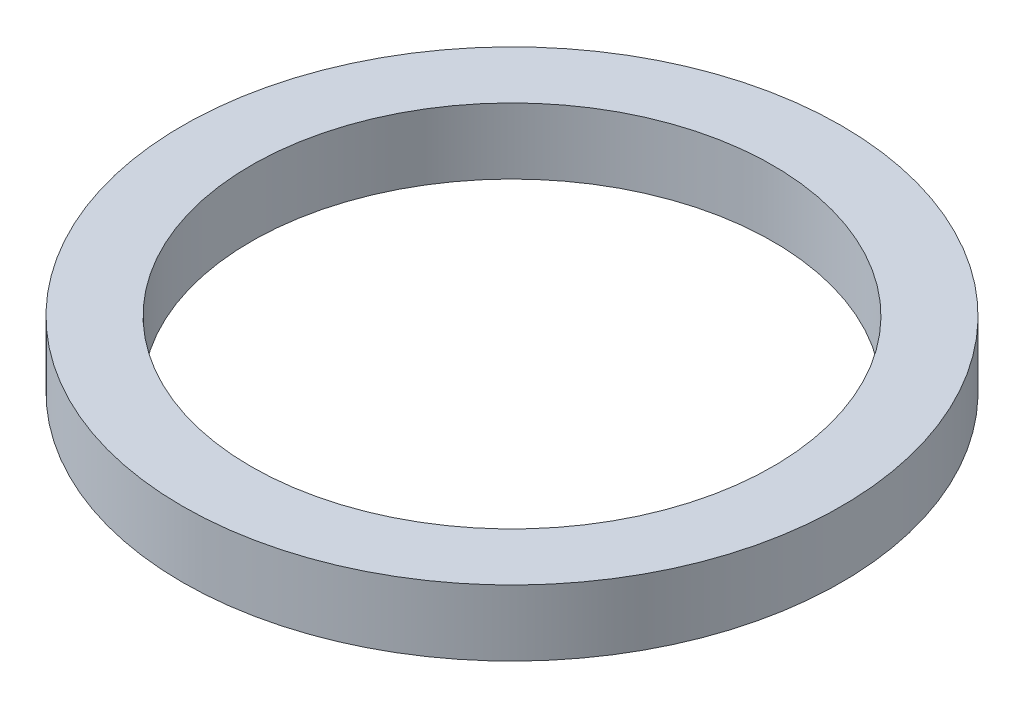
SolidWorks part; units mm, degrees
ref_plane "Front Plane" through (0, 0, 0) normal (0, 0, 1) x (1, 0, 0)
ref_plane "Top Plane" through (0, 0, 0) normal (0, 1, 0) x (1, 0, 0)
ref_plane "Right Plane" through (0, 0, 0) normal (1, 0, 0) x (0, 0, -1)
sketch "Sketch1" plane through (0, 0, 0) normal (0, 1, 0) x (1, 0, 0)
  circle A0 centre (0, 0) radius 60
  dimension "FLANGE_OD" = 120
extrude "Boss-Extrude1" add sketch "Sketch1" along normal blind 12
sketch "Sketch2" plane through (0, 0, 0) normal (0, 1, 0) x (1, 0, 0)
  circle A0 centre (0, 0) radius 47.5
  dimension "BORE_D" = 95
extrude "Cut-Extrude1" cut sketch "Sketch2" along normal through all
sketch "Sketch3" plane through (0, 12, 0) normal (0, 1, 0) x (1, 0, 0)
  circle A0 centre (0, 0) radius 27.226 construction
  circle A1 centre (-27.226, 0) radius 1.6763
  dimension "BOLT_D" = 3.3525
  dimension "BOLT_PCD" = 54.452
extrude "Cut-Extrude2" cut sketch "Sketch3" against normal blind 8.7066 rebuild error yes
pattern_circular "CirPattern1" count 3 over 360 rebuild error yes
